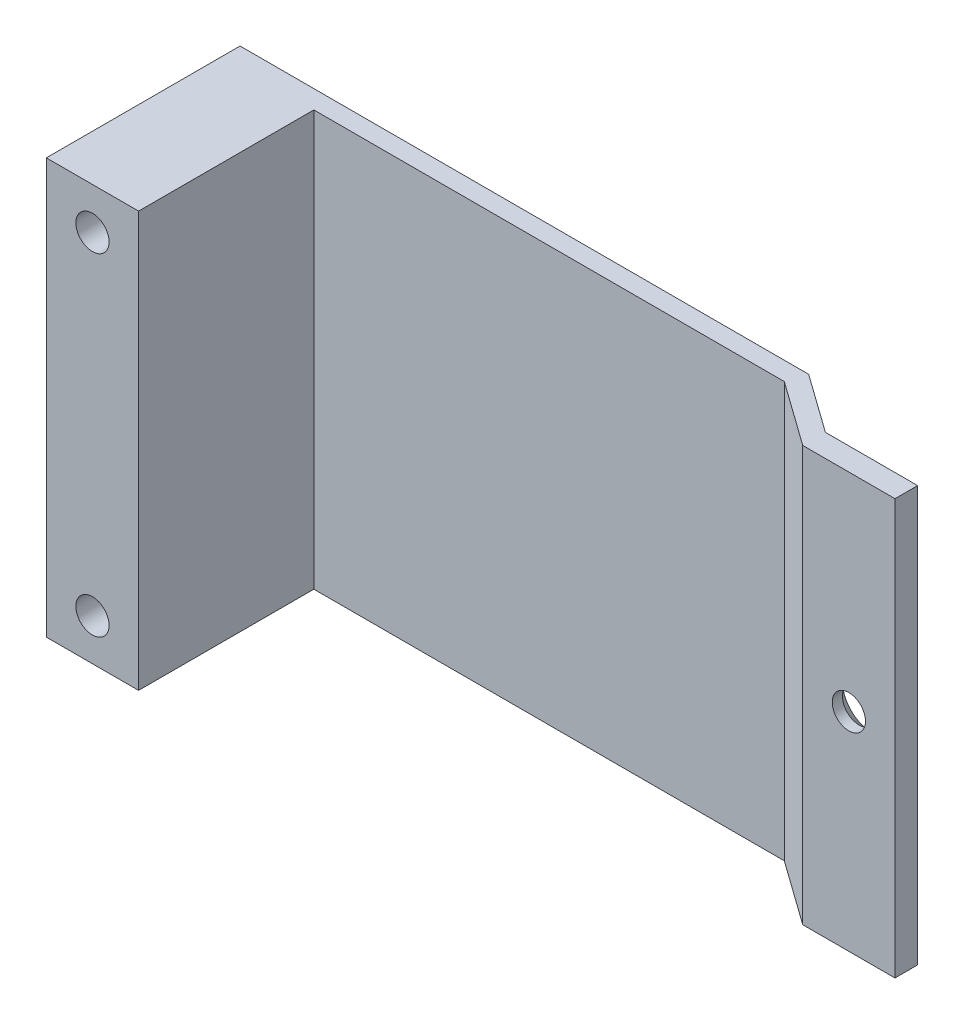
SolidWorks part; units mm, degrees
material "ABS"
ref_plane "Front Plane" through (0, 0, 0) normal (0, 0, 1) x (1, 0, 0)
ref_plane "Top Plane" through (0, 0, 0) normal (0, 1, 0) x (1, 0, 0)
ref_plane "Right Plane" through (0, 0, 0) normal (1, 0, 0) x (0, 0, -1)
sketch "Sketch1" plane through (0, 0, 0) normal (0, 0, 1) x (1, 0, 0)
  line L0 (-29, 22.5) -> (-29, -22.5)
  line L1 (-39, 22.5) -> (39, 22.5)
  line L2 (-39, 22.5) -> (-39, -22.5)
  line L3 (-39, -22.5) -> (39, -22.5)
  line L4 (39, 22.5) -> (39, -22.5)
  line L5 (-39, 22.5) -> (39, -22.5) construction
  line L6 (-39, -22.5) -> (39, 22.5) construction
  line L7 (29, 22.5) -> (29, -22.5)
  circle A0 centre (34, 0) radius 1.65
  circle A1 centre (-34, 0) radius 1.65 construction
  circle A2 centre (-34, -18) radius 1.65
  circle A3 centre (-34, 18) radius 1.65
  point P0 (0, 0)
  dimension "D3" = 3.3
  dimension "D1" = 78
  dimension "D2" = 45
  dimension "D4" = 5
  dimension "D5" = 5
  dimension "D6" = 10
  dimension "D7" = 10
  dimension "D8" = 18
  dimension "D9" = 18
extrude "Boss-Extrude1" add sketch "Sketch1" against normal blind 2 contours L2 L3 L0 L1 A1 | L7 L1 L0 L3 | L1 L7 L3 L4 A0 region at (0, 0, 0) region at (-34, 0, 0) region at (34, 22.039, 0)
extrude "Boss-Extrude2" add sketch "Sketch1<3>" along normal blind 5 contours L2 L3 L0 L1 A1 | L1 L7 L3 L4 A0 region at (-34, 0, 0) region at (34, 22.039, 0)
sketch "Sketch1<3>" plane through (0, 0, 0) normal (0, 0, 1) x (1, 0, 0) same geometry as "Sketch1"
extrude "Boss-Extrude3" add sketch "Sketch1<4>" along normal blind 19 contours L2 L3 L0 L1 A3 A2 region at (-34, 0, 0)
sketch "Sketch1<4>" plane through (0, 0, 0) normal (0, 0, 1) x (1, 0, 0) same geometry as "Sketch1"
chamfer "Chamfer2" distance 7 distance2 5 1 edges at (29, 0, 0) first distance on face at (0, 0, 0)
sketch "Sketch2" plane through (0, -22.5, 0) normal (0, -1, 0) x (1, 0, 0)
  line L1 (-39, -2) -> (39, -2) construction
  line L7 (22.6409, -2) -> (29, 2.5422)
  line L8 (29, 2.5422) -> (39, 2.5422)
  line L9 (39, -2) -> (39, 5) construction
  line L10 (39, 2.5422) -> (39, -2)
  line L11 (39, -2) -> (22.6409, -2)
  line L12 (29, 5) -> (22, 0) construction
  dimension "D2" = 2
extrude "Cut-Extrude1" cut sketch "Sketch2" against normal blind 63
hole_wizard "CSK for M3 Countersunk Flat Head Screw1" positions "Sketch3" profile "Sketch4" countersink size "M3" standard "ISO" end condition through all
sketch "Sketch3" plane through (0, 0, 2.5422) normal (0, 0, -1) x (-1, 0, 0)
  point P0 (-34, 0)
sketch "Sketch4" plane through (34, 0, 2.5422) normal (1, 0, 0) x (0, 1, 0)
  line L0 (0, 0) -> (0, 16.4578)
  line L1 (0, 16.4578) -> (1.8, 16.4578)
  line L2 (1.8, 16.4578) -> (1.8, 1.35)
  line L3 (1.8, 1.35) -> (3.15, 0)
  line L5 (3.15, 0) -> (0, 0)
  line L6 (-1.8, 1.35) -> (-3.15, 0) construction
  line L11 (0, -6.35) -> (0, 107.95) construction
  dimension "Thru Hole Dia." = 3.6
  dimension "Thru Hole Depth" = 16.4578
  dimension "Near C'Sink Dia." = 6.3
  dimension "Near C'Sink Angle" = 90
hole_wizard "CSK for M3 Countersunk Flat Head Screw2" positions "Sketch5" profile "Sketch6" countersink size "M3" standard "ISO" end condition through all
sketch "Sketch5" plane through (0, 0, -2) normal (0, 0, -1) x (-1, 0, 0)
  point P0 (34, -18)
  point P3 (34, 18)
sketch "Sketch6" plane through (-34, -18, -2) normal (1, 0, 0) x (0, 1, 0)
  line L0 (0, 0) -> (0, 21)
  line L1 (0, 21) -> (1.8, 21)
  line L2 (1.8, 21) -> (1.8, 1.35)
  line L3 (1.8, 1.35) -> (3.15, 0)
  line L5 (3.15, 0) -> (0, 0)
  line L6 (-1.8, 1.35) -> (-3.15, 0) construction
  line L11 (0, -6.35) -> (0, 107.95) construction
  dimension "Thru Hole Dia." = 3.6
  dimension "Thru Hole Depth" = 21
  dimension "Near C'Sink Dia." = 6.3
  dimension "Near C'Sink Angle" = 90
